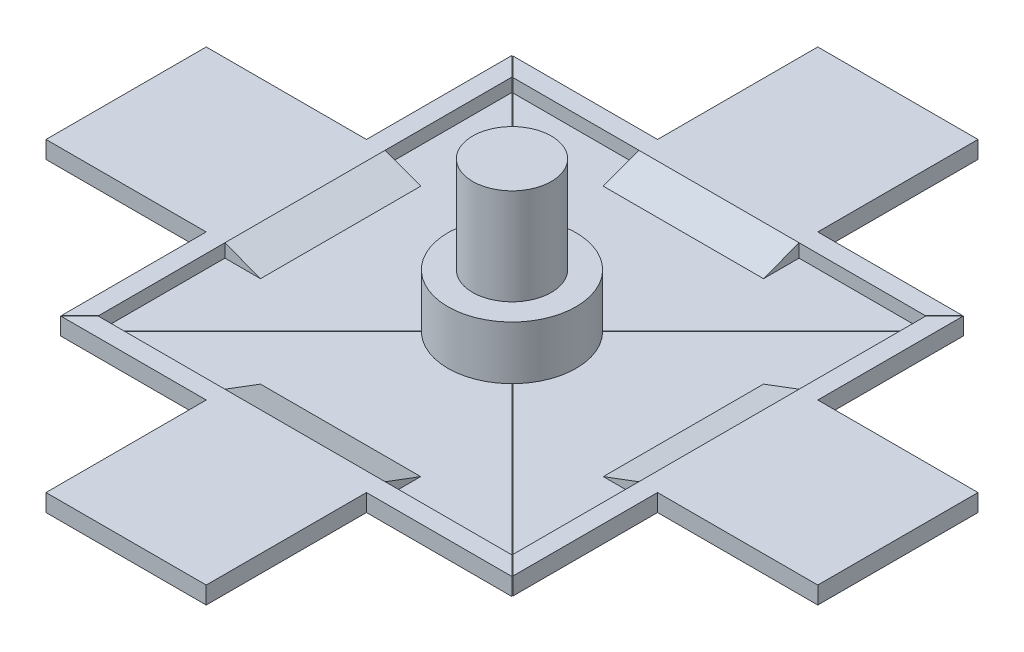
SolidWorks part; units mm, degrees
ref_plane "Front Plane" through (0, 0, 0) normal (0, 0, 1) x (1, 0, 0)
ref_plane "Top Plane" through (0, 0, 0) normal (0, 1, 0) x (1, 0, 0)
ref_plane "Right Plane" through (0, 0, 0) normal (1, 0, 0) x (0, 0, -1)
sketch "Field Layout" plane through (0, 0, 0) normal (0, 1, 0) x (1, 0, 0)
  line L0 (-984.25, -984.25) -> (984.25, -984.25)
  line L1 (-984.25, -984.25) -> (-984.25, 984.25)
  line L2 (-984.25, 984.25) -> (984.25, 984.25)
  line L3 (984.25, 984.25) -> (984.25, -984.25)
  line L4 (-984.25, -984.25) -> (984.25, 984.25) construction
  line L5 (984.25, -984.25) -> (0, 0)
  line L6 (-984.25, -984.25) -> (0, 0)
  line L7 (0, 0) -> (0, -1950.025) construction
  line L8 (-1073.15, 1073.15) -> (1073.15, 1073.15)
  line L9 (-1073.15, 1073.15) -> (-1073.15, -1073.15)
  line L10 (-1073.15, -1073.15) -> (1073.15, -1073.15)
  line L11 (1073.15, 1073.15) -> (1073.15, -1073.15)
  line L12 (-381, -1073.15) -> (381, -1073.15)
  line L13 (-381, -1073.15) -> (-381, -1835.15)
  line L14 (-381, -1835.15) -> (381, -1835.15)
  line L15 (381, -1073.15) -> (381, -1835.15)
  line L16 (-1073.15, 381) -> (-1835.15, 381)
  line L17 (-1073.15, 381) -> (-1073.15, -381)
  line L18 (-1073.15, -381) -> (-1835.15, -381)
  line L19 (-1835.15, 381) -> (-1835.15, -381)
  line L20 (381, 1073.15) -> (381, 1835.15)
  line L21 (381, 1073.15) -> (-381, 1073.15)
  line L22 (-381, 1073.15) -> (-381, 1835.15)
  line L23 (381, 1835.15) -> (-381, 1835.15)
  line L24 (1073.15, -381) -> (1835.15, -381)
  line L25 (1073.15, -381) -> (1073.15, 381)
  line L26 (1073.15, 381) -> (1835.15, 381)
  line L27 (1835.15, -381) -> (1835.15, 381)
  line L28 (381, -1835.15) -> (-381, -1073.15) construction
  line L29 (-152.4, -1746.25) -> (152.4, -1162.05) construction
  line L30 (-152.4, -1746.25) -> (152.4, -1746.25)
  line L31 (-152.4, -1746.25) -> (-152.4, -1162.05)
  line L32 (-152.4, -1162.05) -> (152.4, -1162.05)
  line L33 (152.4, -1746.25) -> (152.4, -1162.05)
  line L34 (-984.25, 381) -> (-815.1118, 381)
  line L35 (-381, -984.25) -> (381, -984.25)
  line L36 (-381, -984.25) -> (-381, -815.1118)
  line L37 (-381, -815.1118) -> (381, -815.1118)
  line L38 (381, -984.25) -> (381, -815.1118)
  line L39 (-815.1118, 381) -> (-815.1118, -381)
  line L40 (-984.25, -381) -> (-815.1118, -381)
  line L41 (-1746.25, 152.4) -> (-1162.05, 152.4)
  line L42 (-1746.25, 152.4) -> (-1746.25, -152.4)
  line L43 (-1746.25, -152.4) -> (-1162.05, -152.4)
  line L44 (-1162.05, 152.4) -> (-1162.05, -152.4)
  line L45 (381, 984.25) -> (381, 815.1118)
  line L46 (381, 815.1118) -> (-381, 815.1118)
  line L47 (-381, 984.25) -> (-381, 815.1118)
  line L48 (152.4, 1746.25) -> (152.4, 1162.05)
  line L49 (152.4, 1746.25) -> (-152.4, 1746.25)
  line L50 (-152.4, 1746.25) -> (-152.4, 1162.05)
  line L51 (152.4, 1162.05) -> (-152.4, 1162.05)
  line L52 (984.25, -381) -> (815.1118, -381)
  line L53 (815.1118, -381) -> (815.1118, 381)
  line L54 (984.25, 381) -> (815.1118, 381)
  line L55 (1746.25, -152.4) -> (1162.05, -152.4)
  line L56 (1746.25, -152.4) -> (1746.25, 152.4)
  line L57 (1746.25, 152.4) -> (1162.05, 152.4)
  line L58 (1162.05, -152.4) -> (1162.05, 152.4)
  circle A0 centre (0, 0) radius 304.8
  point P2 (0, 0)
  point P16 (0, -1454.15)
  point P32 (0, 0)
  point P66 (0, 0)
  dimension "D3" = 609.6
  dimension "D1" = 1968.5
  dimension "D2" = 1968.5
  dimension "D4" = 88.9
  dimension "D5" = 88.9
  dimension "D6" = 762
  dimension "D8" = 584.2
  dimension "D9" = 304.8
  dimension "D7" = 4
  dimension "D10" = 4
extrude "Plywood Base" add sketch "Field Layout" against normal blind 19.05 contours L16 L19 L18 L9 L41 L44 L43 L42 | L44 L41 L42 L43 | L11 L8 L9 L10 L2 L3 L0 L1 | L1 L40 L39 L34 | A0 L5 L3 L52 L53 L54 L2 L45 L46 L47 L1 L34 L39 L40 L6 | A0 L6 L0 L36 L37 L38 L5 | L6 A0 L5 | L5 A0 L6 | L0 L38 L37 L36 | L30 L33 L32 L31 | L15 L10 L13 L14 L33 L30 L31 L32 | L3 L54 L53 L52 | L24 L27 L26 L11 L55 L58 L57 L56 | L58 L55 L56 L57 | L2 L47 L46 L45 | L20 L23 L22 L8 L48 L51 L50 L49 | L51 L48 L49 L50 region at (0, 0, 660.2665) region at (-956.4112, 0, 682.625) region at (0, 0, 899.6809) region at (-899.6809, 0, 0) region at (0, 0, -60.9814) region at (0, 0, 182.9443) region at (899.6809, 0, 0) region at (0, 0, -899.6809) region at (-727.075, 0, -1042.7967) region at (-370.2237, 0, -1454.15) region at (-1083.9263, 0, 0) region at (1454.15, 0, -370.2237) region at (0, 0, 1083.9263) region at (0, 0, 1454.15) region at (-1454.15, 0, 0) region at (0, 0, -1454.15) region at (1454.15, 0, 0)
extrude "Raised Base" add sketch "Field Layout<3>" along normal blind 63.5 contours L16 L19 L18 L9 L41 L44 L43 L42 | L44 L41 L42 L43 | L11 L8 L9 L10 L2 L3 L0 L1 | L15 L10 L13 L14 L33 L30 L31 L32 | L30 L33 L32 L31 | L58 L55 L56 L57 | L24 L27 L26 L11 L55 L58 L57 L56 | L51 L48 L49 L50 | L20 L23 L22 L8 L48 L51 L50 L49 region at (-727.075, 0, -1042.7967) region at (-370.2237, 0, -1454.15) region at (-1083.9263, 0, 0) region at (1454.15, 0, -370.2237) region at (0, 0, 1083.9263) region at (0, 0, 1454.15) region at (-1454.15, 0, 0) region at (0, 0, -1454.15) region at (1454.15, 0, 0)
sketch "Field Layout<3>" plane through (0, 0, 0) normal (0, 1, 0) x (1, 0, 0) same geometry as "Field Layout"
extrude "Ramp Extrude" add sketch "Field Layout<4>" along normal blind 63.5 contours L0 L38 L37 L36 region at (0, 0, 899.6809)
sketch "Field Layout<4>" plane through (0, 0, 0) normal (0, 1, 0) x (1, 0, 0) same geometry as "Field Layout"
sketch "Sketch3" plane through (381, 0, 0) normal (1, 0, 0) x (0, 0, -1)
  line L4 (-984.25, 63.5) -> (-815.1118, 0)
  line L8 (-984.25, 0) -> (-815.1118, 0)
  line L9 (-815.1118, 0) -> (-815.1118, 63.5)
  line L10 (-815.1118, 63.5) -> (-984.25, 63.5)
  line L11 (-984.25, 63.5) -> (-984.25, 0)
  line L12 (-984.25, 0) -> (-815.1118, 0)
  line L13 (-815.1118, 0) -> (-815.1118, 63.5)
  line L14 (-815.1118, 63.5) -> (-984.25, 63.5)
  line L15 (-984.25, 63.5) -> (-984.25, 0)
  line M6 (-815.1118, 0) -> (-815.1118, 63.5)
  line M7 (-815.1118, 63.5) -> (-984.25, 63.5)
  dimension "D1" = 0
extrude "Cut ramp slope" cut sketch "Sketch3" against normal up to next contours L4 M7 M6 region at (381, 42.3333, 871.4912)
pattern_circular "Copy Ramp Slope" count 4 over 360 about axis through (0, -19.05, 0) along (0, -1, 0) of "Ramp Extrude", "Cut ramp slope"
sketch "Sketch5" plane through (0, 0, 0) normal (0, 1, 0) x (1, 0, 0)
  circle A0 centre (0, 0) radius 304.8
  dimension "D1" = 609.6
extrude "Boss-Extrude1" add sketch "Sketch5" along normal blind 254 separate body
sketch "Sketch4" plane through (0, 0, 0) normal (0, 1, 0) x (1, 0, 0)
  line L0 (-984.25, -984.25) -> (984.25, 984.25)
  line L1 (-984.25, 984.25) -> (984.25, -984.25)
  line L3 (984.25, 984.25) -> (1073.15, 1073.15)
  line L4 (-984.25, -984.25) -> (-1073.15, -1073.15)
  line L5 (984.25, -984.25) -> (1073.15, -1073.15)
  line L6 (-984.25, 984.25) -> (-1073.15, 1073.15)
extrude "Cut-Extrude-Thin1" cut sketch "Sketch4" against normal through all both and the other way through all thin thin type one direction wall 2.54
sketch "Sketch6" plane through (0, 254, 0) normal (0, 1, 0) x (1, 0, 0)
  circle A0 centre (0, 0) radius 187.2268
extrude "Boss-Extrude2" add sketch "Sketch6" along normal blind 457.2
